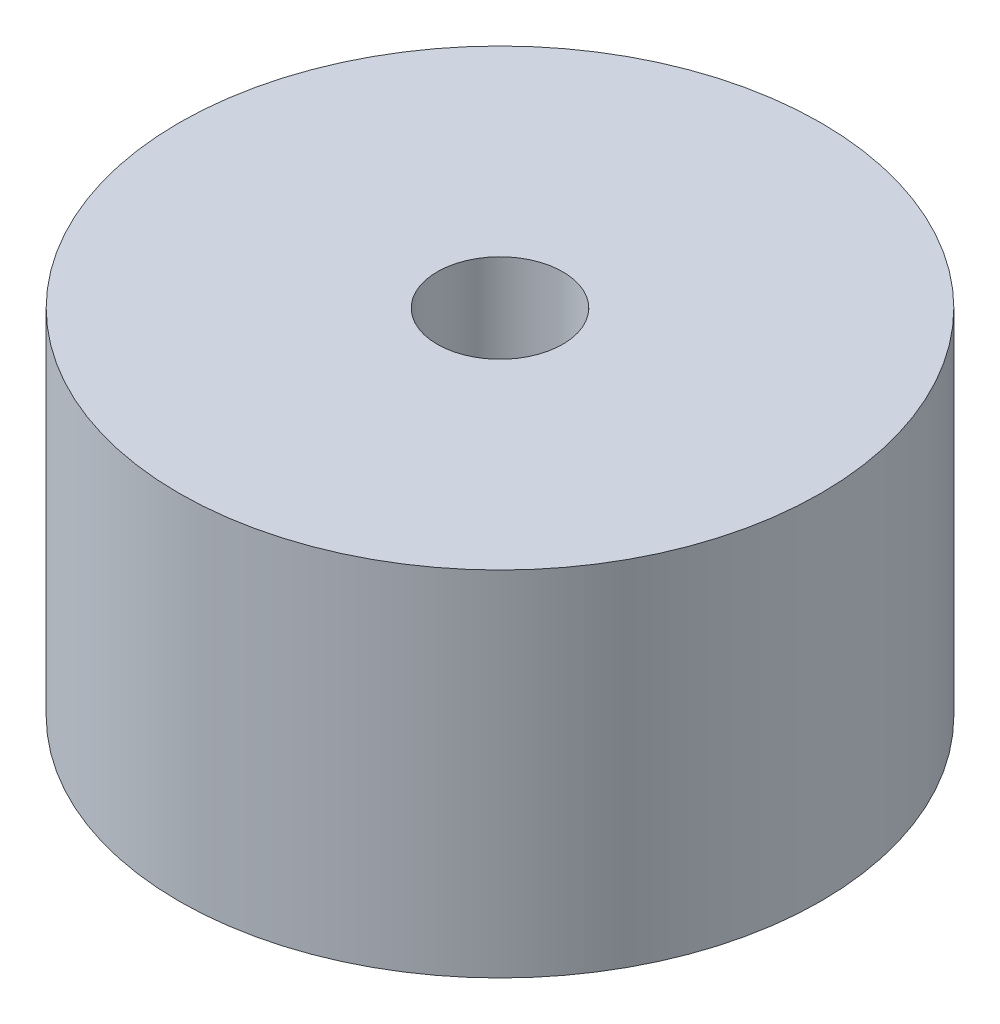
SolidWorks part; units mm, degrees
ref_plane "Front Plane" through (0, 0, 0) normal (0, 0, 1) x (1, 0, 0)
ref_plane "Top Plane" through (0, 0, 0) normal (0, 1, 0) x (1, 0, 0)
ref_plane "Right Plane" through (0, 0, 0) normal (1, 0, 0) x (0, 0, -1)
sketch "Sketch1" plane through (0, 0, 0) normal (0, 1, 0) x (1, 0, 0)
  circle A0 centre (0, 0) radius 1.6
  circle A1 centre (0, 0) radius 8.175
  circle A2 centre (0, 0) radius 8.175
  point P25 (0, 0)
extrude "Boss-Extrude1" add sketch "Sketch1" along normal blind 6 and the other way blind 3 contours A1 A0 region at (-7.9438, 0, 0)
extrude "Boss-Extrude2" add sketch "Sketch1<3>" against normal blind 3 separate body contours A2 A1 region at (-7.9438, 0, 0)
sketch "Sketch1<3>" plane through (0, 0, 0) normal (0, 1, 0) x (1, 0, 0) same geometry as "Sketch1"
sketch "Sketch2" plane through (0, 0, 0) normal (1, 0, 0) x (0, 0, -1)
  line L0 (0, 0) -> (0, 2)
  line L1 (0, 4) -> (0, 6)
  circle A0 centre (0, 3) radius 1
  dimension "D1" = 2
extrude "Cut-Extrude1" cut sketch "Sketch2" against normal blind 15 contours A0
sketch "Sketch3" plane through (0, -3, 0) normal (0, -1, 0) x (1, 0, 0)
  circle A0 centre (0, 9.6613) radius 0.75
  circle A2 centre (9.1884, 2.9855) radius 0.75
  circle A3 centre (5.6787, -7.8161) radius 0.75
  circle A4 centre (-5.6787, -7.8161) radius 0.75
  circle A5 centre (-9.1884, 2.9855) radius 0.75
  point P14 (0, 0)
  dimension "D1" = 5
sketch "Sketch4" plane through (0, -3, 0) normal (0, -1, 0) x (1, 0, 0)
  circle A0 centre (0, 0) radius 3.5
extrude "Boss-Extrude3" add sketch "Sketch4" along normal blind 3 contours A0
extrude "Cut-Extrude2" cut sketch "Sketch1<7>" against normal blind 13 contours A0
sketch "Sketch1<7>" plane through (0, 0, 0) normal (0, 1, 0) x (1, 0, 0) same geometry as "Sketch1"
extrude "Cut-Extrude3" [suppressed] cut sketch "Sketch3" against normal blind 10
